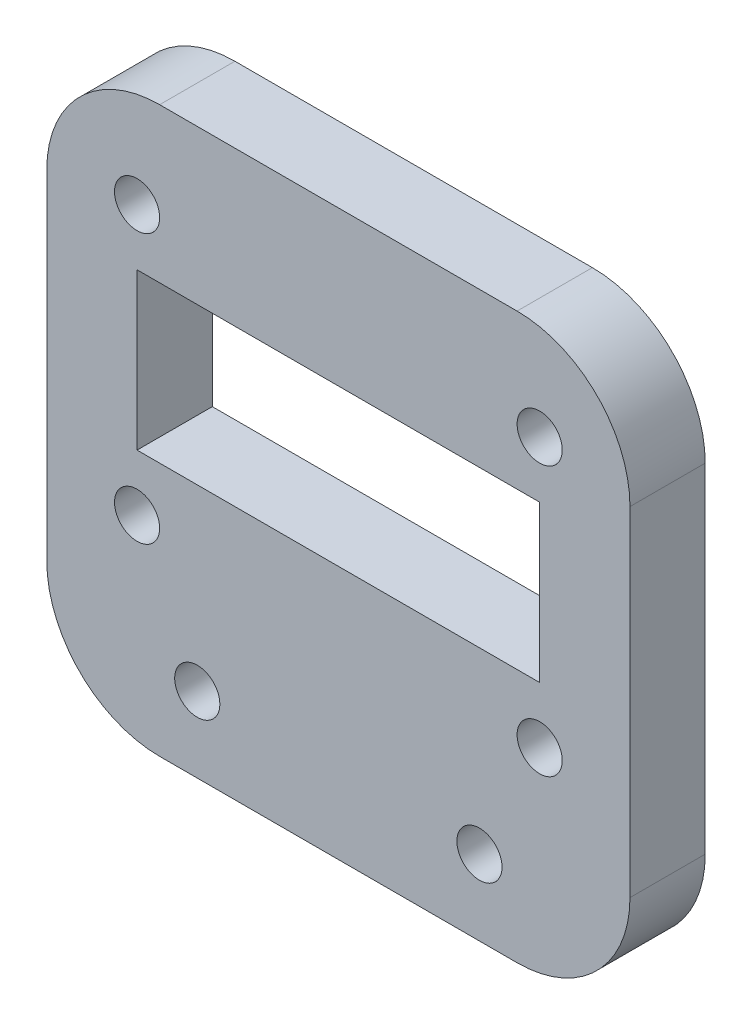
SolidWorks part; units mm, degrees
ref_plane "Front Plane" through (0, 0, 0) normal (0, 0, 1) x (1, 0, 0)
ref_plane "Top Plane" through (0, 0, 0) normal (0, 1, 0) x (1, 0, 0)
ref_plane "Right Plane" through (0, 0, 0) normal (1, 0, 0) x (0, 0, -1)
sketch "Sketch1" plane through (0, 0, 0) normal (0, 0, 1) x (1, 0, 0)
  line L0 (0, 2.65) -> (0, 0) construction
  line L5 (-12.5, -12) -> (12.5, -12) construction
  line L6 (-12.5, -12) -> (-12.5, 12) construction
  line L7 (-12.5, 12) -> (12.5, 12) construction
  line L8 (12.5, -12) -> (12.5, 12) construction
  line L9 (-12.5, -12) -> (12.5, 12) construction
  line L10 (-12.5, 12) -> (12.5, -12) construction
  line L15 (-15.5, -15) -> (15.5, -15)
  line L16 (-15.5, -15) -> (-15.5, 15)
  line L17 (-15.5, 15) -> (15.5, 15)
  line L18 (15.5, -15) -> (15.5, 15)
  line L23 (-15.5, -15) -> (15.5, 15) construction
  line L24 (-15.5, 15) -> (15.5, -15) construction
  line L25 (10.7, 9.8) -> (-10.7, 9.8) construction
  line L26 (10.7, 9.8) -> (10.7, -4.5)
  line L27 (10.7, -4.5) -> (-10.7, -4.5) construction
  line L28 (-10.7, 9.8) -> (-10.7, -4.5) construction
  line L29 (10.7, 9.8) -> (-10.7, -4.5) construction
  line L30 (10.7, -4.5) -> (-10.7, 9.8) construction
  line L31 (-9.5, 9.8) -> (9.5, 9.8) construction
  line L33 (-10.7, 8.6) -> (-10.7, -3.3)
  line L35 (-11.9, 9.8) -> (-12.5, 9.8) construction
  line L38 (-10.7, 11) -> (-10.7, 12) construction
  line L42 (-7.5, -11) -> (7.5, -11) construction
  line L44 (0, -11) -> (0, -12) construction
  line L46 (-10.7, -1.5) -> (10.7, -1.5)
  line L47 (-10.7, -1.5) -> (-10.7, 6.8)
  line L48 (-10.7, 6.8) -> (10.7, 6.8)
  line L49 (10.7, -1.5) -> (10.7, 6.8)
  line L50 (-10.7, -1.5) -> (10.7, 6.8) construction
  line L51 (-10.7, 6.8) -> (10.7, -1.5) construction
  circle A0 centre (-10.7, 9.8) radius 1.2
  circle A1 centre (10.7, 9.8) radius 1.2
  circle A2 centre (10.7, -4.5) radius 1.2
  circle A3 centre (-10.7, -4.5) radius 1.2
  circle A4 centre (-7.5, -11) radius 1.2
  circle A5 centre (7.5, -11) radius 1.2
  circle A6 centre (-7.5, -11) radius 2.8
  circle A7 centre (7.5, -11) radius 2.8
  point P0 (0, 0)
  point P5 (0, 2.65)
  point P6 (0, 0)
  dimension "D1" = 25
  dimension "D2" = 24
  dimension "D10" = 15
  dimension "D7" = 2.4
  dimension "D9" = 2.4
  dimension "D14" = 1.6
  dimension "D15" = 1.6
  dimension "D3" = 3
  dimension "D4" = 3
  dimension "D5" = 19
  dimension "D6" = 11.9
  dimension "D8" = 1
  dimension "D11" = 1
  dimension "D12" = 3
  dimension "D13" = 0
extrude "Boss-Extrude1" add sketch "Sketch1" along normal blind 4 contours L15 L18 L17 L16 A5 A4 A3 L33 A0 L48 A1 L26 A2 L46 | A6 A4 | A7 A5 region at (-15.0686, 0, 0) region at (-10.2208, -11, 0) region at (4.7792, -11, 0)
extrude "Cut-Extrude1" cut sketch "Sketch1<6>" along normal blind 2 contours A6 A4 | A7 A5 region at (-10.2208, -11, 0) region at (4.7792, -11, 0)
sketch "Sketch1<6>" plane through (0, 0, 0) normal (0, 0, 1) x (1, 0, 0) same geometry as "Sketch1"
fillet "Fillet1" radius 6 4 edges at (15.5, -15, 2) (-15.5, -15, 2) (-15.5, 15, 2) (15.5, 15, 2)
